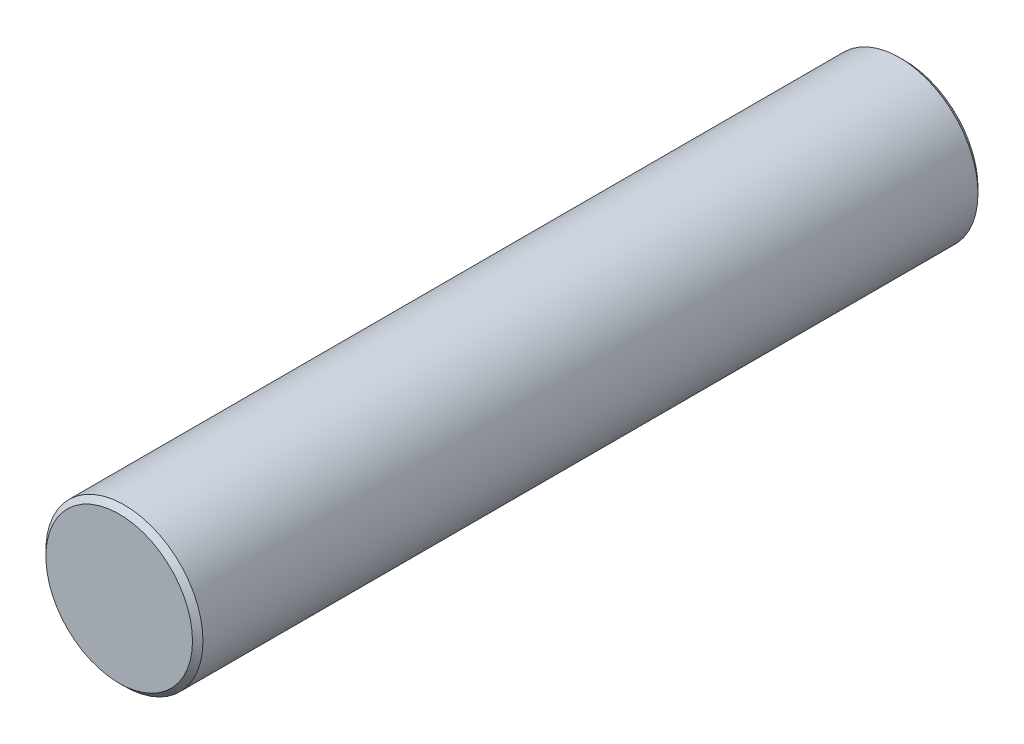
SolidWorks part; units mm, degrees
ref_plane "Front Plane" through (0, 0, 0) normal (0, 0, 1) x (1, 0, 0)
ref_plane "Top Plane" through (0, 0, 0) normal (0, 1, 0) x (1, 0, 0)
ref_plane "Right Plane" through (0, 0, 0) normal (1, 0, 0) x (0, 0, -1)
sketch "Sketch1" plane through (0, 0, 0) normal (0, 0, 1) x (1, 0, 0)
  circle A0 centre (0, 0) radius 3
  dimension "D1" = 6
extrude "Boss-Extrude1" add sketch "Sketch1" along normal blind 30
chamfer "Chamfer1" distance 0.2 angle 45 2 edges at (3, 0, 0) (3, 0, 30)
